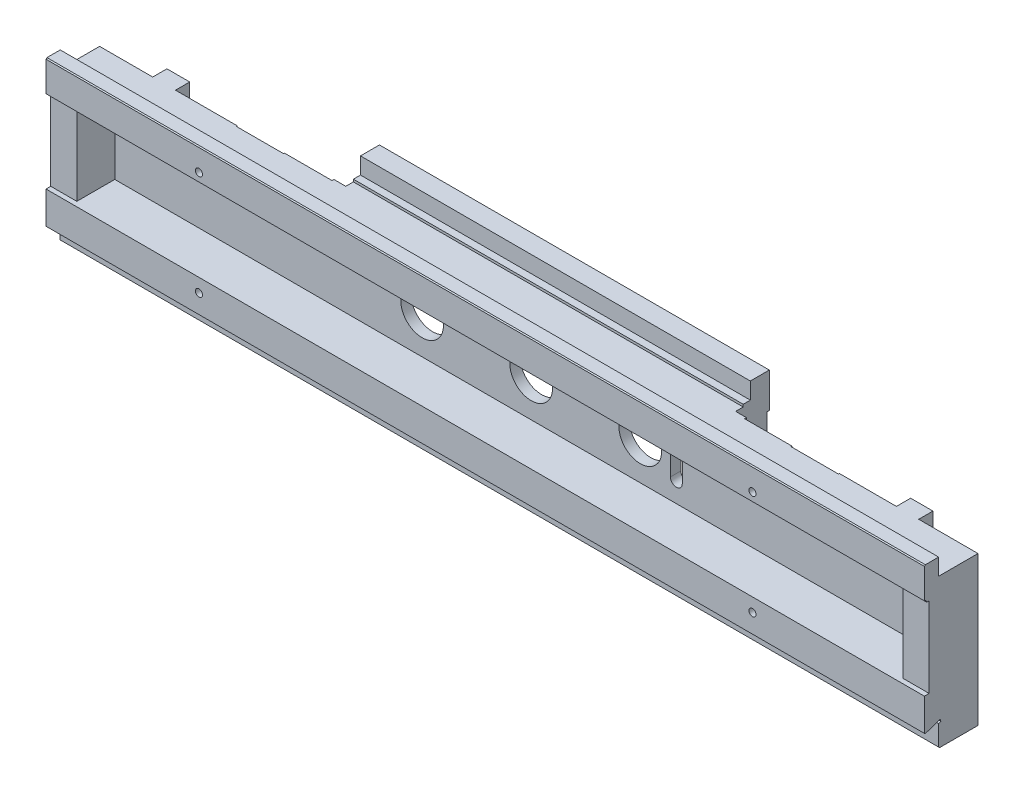
SolidWorks part; units mm, degrees
ref_plane "前视基准面" through (0, 0, 0) normal (0, 0, 1) x (1, 0, 0)
ref_plane "上视基准面" through (0, 0, 0) normal (0, 1, 0) x (1, 0, 0)
ref_plane "右视基准面" through (0, 0, 0) normal (1, 0, 0) x (0, 0, -1)
sketch "草图2" plane through (0, 0, 0) normal (1, 0, 0) x (0, 0, -1)
  line L0 (-76.2602, 62.6385) -> (-46.2602, 62.6385)
  line L1 (-46.2602, 62.6385) -> (-46.2602, 27.6385)
  line L2 (-46.2602, 27.6385) -> (36.7398, 27.6385)
  line L3 (36.7398, 27.6385) -> (36.7398, -286.3615)
  line L4 (36.7398, -286.3615) -> (-46.2602, -286.3615)
  line L5 (-46.2602, -286.3615) -> (-46.2602, -241.3615)
  line L6 (-76.2602, 62.6385) -> (-76.2602, -2.3615)
  line L9 (-66.2602, -176.3615) -> (-76.2602, -176.3615)
  line L10 (-46.2602, -241.3615) -> (-41.5305, -239.7399)
  line L11 (-41.5305, -239.7399) -> (-43.1521, -235.0102)
  line L12 (-43.1521, -235.0102) -> (-76.2602, -246.3615)
  line L13 (-76.2602, -246.3615) -> (-76.2602, -176.3615)
  line L14 (-76.2602, -2.3615) -> (-71.2602, -2.3615)
  line L15 (-71.2602, -2.3615) -> (-71.2602, -7.3574)
  line L17 (-71.2602, -7.3574) -> (-66.2602, -7.3574)
  line L18 (-66.2602, -7.3574) -> (-66.2602, -176.3615)
  dimension "D1" = 30
  dimension "D2" = 35
  dimension "D3" = 83
  dimension "D4" = 314
  dimension "D5" = 83
  dimension "D6" = 45
  dimension "D7" = 70
  dimension "D8" = 10
  dimension "D9" = 65
  dimension "D10" = 5
  dimension "D11" = 5
  dimension "D12" = 35
  dimension "D13" = 5
  dimension "D14" = 5
  dimension "D15" = 4.9959
extrude "凸台-拉伸1" add sketch "草图2" along normal blind 1852
fillet "圆角1" radius 5 1 edges at (926, -2.3615, 71.2602)
chamfer "倒角1" distance 2 angle 45 3 edges at (926, -286.3615, 46.2602) (926, -246.3615, 76.2602) (926, 62.6385, 76.2602) first distance on face at (926, -263.8615, 46.2602) first distance on face at (926, -211.3615, 76.2602) first distance on face at (926, 62.6385, 61.2602)
ref_plane "基准面1" through (1337, 0, 0) normal (1, 0, 0) x (0, 0, -1)
sketch "草图4" plane through (1337, 0, 0) normal (1, 0, 0) x (0, 0, -1)
  line L0 (36.7398, 27.6385) -> (56.7398, 27.6385)
  line L1 (56.7398, 27.6385) -> (56.7398, 32.6385)
  line L2 (56.7398, 32.6385) -> (71.7398, 32.6385)
  line L3 (71.7398, 32.6385) -> (71.7398, 67.6385)
  line L4 (71.7398, 67.6385) -> (111.7398, 67.6385)
  line L5 (111.7398, 67.6385) -> (111.7398, -326.3615)
  line L6 (111.7398, -326.3615) -> (71.7398, -326.3615)
  line L7 (71.7398, -326.3615) -> (71.7398, -291.3615)
  line L8 (71.7398, -291.3615) -> (56.7398, -291.3615)
  line L9 (56.7398, -291.3615) -> (56.7398, -286.3615)
  line L10 (56.7398, -286.3615) -> (36.7398, -286.3615)
  line L11 (36.7398, -286.3615) -> (36.7398, 27.6385)
  dimension "D1" = 20
  dimension "D2" = 5
  dimension "D3" = 15
  dimension "D4" = 35
  dimension "D5" = 40
  dimension "D6" = 20
  dimension "D7" = 5
  dimension "D8" = 15
  dimension "D9" = 35
extrude "凸台-拉伸2" add sketch "草图4" against normal blind 822
sketch "草图5" plane through (0, 0, -36.7398) normal (0, 0, -1) x (-1, 0, 0)
  line L0 (-1852, 27.6385) -> (-1337, 27.6385) construction
  line L1 (-1727, 27.6385) -> (-1680, 27.6385)
  line L2 (-1727, 27.6385) -> (-1727, -286.3615)
  line L3 (-1727, -286.3615) -> (-1680, -286.3615)
  line L4 (-1680, 27.6385) -> (-1680, -286.3615)
  line L5 (-1852, -286.3615) -> (-1337, -286.3615) construction
  line L6 (-1852, -286.3615) -> (-1852, 27.6385) construction
  dimension "D1" = 47
  dimension "D2" = 125
extrude "凸台-拉伸3" add sketch "草图5" along normal blind 30
sketch "草图7" plane through (0, 0, -36.7398) normal (0, 0, -1) x (-1, 0, 0)
  line L0 (-1680, 27.6385) -> (-1337, 27.6385) construction
  line L1 (-1560, 27.6385) -> (-1460, 27.6385)
  line L2 (-1560, 27.6385) -> (-1560, -286.3615)
  line L3 (-1560, -286.3615) -> (-1460, -286.3615)
  line L4 (-1460, 27.6385) -> (-1460, -286.3615)
  line L5 (-1680, -286.3615) -> (-1337, -286.3615) construction
  line L6 (-1680, -286.3615) -> (-1680, 27.6385) construction
  dimension "D1" = 100
  dimension "D2" = 120
extrude "切除-拉伸1" cut sketch "草图7" against normal blind 2
sketch "草图8" plane through (0, 0, -36.7398) normal (0, 0, -1) x (-1, 0, 0)
  line L0 (-1852, 27.6385) -> (0, 27.6385) construction
  line L1 (-1360, 27.6385) -> (-1337, 27.6385)
  line L2 (-1360, 27.6385) -> (-1360, -286.3615)
  line L3 (-1360, -286.3615) -> (-1337, -286.3615)
  line L4 (-1337, 27.6385) -> (-1337, -286.3615)
  line L5 (-1337, 62.15) -> (-1337, -62.15) construction
  line L6 (-1460, -286.3615) -> (-1337, -286.3615) construction
  dimension "D1" = 23
extrude "凸台-拉伸4" add sketch "草图8" along normal blind 4
sketch "草图9" plane through (0, 0, -36.7398) normal (0, 0, -1) x (-1, 0, 0)
  line L0 (-515, 27.6385) -> (0, 27.6385) construction
  line L1 (-160, 27.6385) -> (-112, 27.6385)
  line L2 (-160, 27.6385) -> (-160, -286.3615)
  line L3 (-160, -286.3615) -> (-112, -286.3615)
  line L4 (-112, 27.6385) -> (-112, -286.3615)
  line L5 (-515, -286.3615) -> (0, -286.3615) construction
  line L6 (0, -286.3615) -> (0, 27.6385) construction
  dimension "D1" = 48
  dimension "D2" = 112
extrude "凸台-拉伸5" add sketch "草图9" along normal blind 30
sketch "草图10" plane through (0, 0, -36.7398) normal (0, 0, -1) x (-1, 0, 0)
  line L0 (-515, 27.6385) -> (-160, 27.6385) construction
  line L1 (-390, 27.6385) -> (-290, 27.6385)
  line L2 (-390, 27.6385) -> (-390, -286.3615)
  line L3 (-390, -286.3615) -> (-290, -286.3615)
  line L4 (-290, 27.6385) -> (-290, -286.3615)
  line L5 (-515, -286.3615) -> (-160, -286.3615) construction
  line L6 (-160, 27.6385) -> (-160, -286.3615) construction
  dimension "D1" = 130
  dimension "D2" = 100
extrude "切除-拉伸2" cut sketch "草图10" against normal blind 2
sketch "草图11" plane through (0, 0, -36.7398) normal (0, 0, -1) x (-1, 0, 0)
  line L0 (-515, -286.3615) -> (-390, -286.3615) construction
  line L1 (-515, 27.6385) -> (-490, 27.6385)
  line L2 (-515, 27.6385) -> (-515, -286.3615)
  line L3 (-515, -286.3615) -> (-490, -286.3615)
  line L4 (-490, 27.6385) -> (-490, -286.3615)
  dimension "D1" = 25
extrude "凸台-拉伸6" add sketch "草图11" along normal blind 4
sketch "草图12" plane through (0, 0, 66.2602) normal (0, 0, 1) x (1, 0, 0)
  line L0 (1852, -7.3574) -> (0, -7.3574) construction
  line L1 (55, -7.3574) -> (1797, -7.3574)
  line L2 (55, -7.3574) -> (55, -176.3615)
  line L3 (55, -176.3615) -> (1797, -176.3615)
  line L4 (1797, -7.3574) -> (1797, -176.3615)
  line L5 (1852, -176.3615) -> (0, -176.3615) construction
  line L6 (0, -7.3574) -> (0, -176.3615) construction
  line L7 (1852, -7.3574) -> (1852, -176.3615) construction
  dimension "D1" = 55
  dimension "D2" = 55
extrude "切除-拉伸3" cut sketch "草图12" against normal blind 80
sketch "草图13" plane through (0, 0, -111.7398) normal (0, 0, -1) x (-1, 0, 0)
  line L0 (-1337, 62.15) -> (-1337, -62.15) construction
  line L1 (-1337, -6.3615) -> (-515, -6.3615)
  line L2 (-1337, -6.3615) -> (-1337, -245.3615)
  line L3 (-1337, -245.3615) -> (-515, -245.3615)
  line L4 (-515, -6.3615) -> (-515, -245.3615)
  line L5 (-515, -326.3615) -> (-515, 67.6385) construction
  line L6 (-515, 67.6385) -> (-1337, 67.6385) construction
  line L7 (-515, -326.3615) -> (-1337, -326.3615) construction
  dimension "D1" = 74
  dimension "D2" = 81
extrude "切除-拉伸4" cut sketch "草图13" against normal blind 5
sketch "草图14" plane through (0, 0, -106.7398) normal (0, 0, -1) x (-1, 0, 0)
  line L0 (-515, -6.3615) -> (-1337, -6.3615) construction
  line L1 (-1294, -16.3615) -> (-558, -16.3615)
  line L2 (-1294, -16.3615) -> (-1294, -235.3615)
  line L3 (-1294, -235.3615) -> (-558, -235.3615)
  line L4 (-558, -16.3615) -> (-558, -235.3615)
  line L5 (-1337, -245.3615) -> (-515, -245.3615) construction
  line L6 (-515, -245.3615) -> (-515, -6.3615) construction
  line L7 (-1337, 62.15) -> (-1337, -62.15) construction
  dimension "D1" = 10
  dimension "D2" = 10
  dimension "D3" = 43
  dimension "D4" = 43
extrude "切除-拉伸5" cut sketch "草图14" against normal blind 71
sketch "草图15" plane through (0, 0, -35.7398) normal (0, 0, -1) x (-1, 0, 0)
  line L0 (-1294, -16.3615) -> (-1294, -235.3615) construction
  line L6 (-558, -16.3615) -> (-1294, -16.3615) construction
  line L8 (-558, -16.3615) -> (-1294, -16.3615) construction
  line L9 (-558, -235.3615) -> (-558, -16.3615) construction
  line L11 (-1226.5, -48.8615) -> (-1226.5, -133.8615)
  line L12 (-1251.5, -48.8615) -> (-1251.5, -133.8615)
  circle A3 centre (-1163, -96.3615) radius 45
  circle A4 centre (-933, -96.3615) radius 45
  circle A5 centre (-703, -96.3615) radius 45
  arc A6 (-1226.5, -48.8615) -> (-1251.5, -48.8615) centre (-1239, -48.8615) ccw
  arc A7 (-1251.5, -133.8615) -> (-1226.5, -133.8615) centre (-1239, -133.8615) ccw
  dimension "D1" = 80
  dimension "D2" = 90
  dimension "D3" = 80
  dimension "D4" = 80
  dimension "D5" = 230
  dimension "D7" = 145
  dimension "D8" = 25
  dimension "D9" = 32.5
  dimension "D10" = 55
  dimension "D6" = 230
  dimension "D11" = 85
extrude "切除-拉伸6" cut sketch "草图15" against normal through all
sketch "草图16" plane through (0, -235.3615, 0) normal (0, 1, 0) x (1, 0, 0)
  line L0 (558, 35.7398) -> (558, 106.7398) construction
  line L1 (1294, 35.7398) -> (558, 35.7398)
  line L2 (1294, 35.7398) -> (1294, 76.7398)
  line L3 (1294, 76.7398) -> (558, 76.7398)
  line L4 (558, 35.7398) -> (558, 76.7398)
  line L5 (1337, 106.7398) -> (515, 106.7398) construction
  dimension "D1" = 30
extrude "切除-拉伸7" cut sketch "草图16" against normal blind 20
sketch "草图17" plane through (0, 0, -66.7398) normal (0, 0, -1) x (-1, 0, 0)
  line L0 (-1680, 27.6385) -> (-1727, 27.6385) construction
  line L1 (-1727, 27.6385) -> (-1727, -286.3615) construction
  line L2 (-1727, 27.6385) -> (-1727, -286.3615) construction
  line L3 (-1852, 27.6385) -> (0, 27.6385) construction
  line L4 (-112, -286.3615) -> (-112, 27.6385) construction
  line L5 (-112, -286.3615) -> (-112, 27.6385) construction
  circle A0 centre (-1707, -2.3615) radius 7.5
  circle A1 centre (-1707, -132.3615) radius 7.5
  circle A2 centre (-1707, -262.3615) radius 7.5
  circle A3 centre (-132, -2.3615) radius 7.5
  circle A4 centre (-132, -132.3615) radius 7.5
  circle A5 centre (-132, -262.3615) radius 7.5
  dimension "D1" = 15
  dimension "D2" = 15
  dimension "D3" = 15
  dimension "D10" = 15
  dimension "D11" = 15
  dimension "D12" = 15
  dimension "D13" = 30
  dimension "D4" = 30
  dimension "D5" = 20
  dimension "D6" = 20
  dimension "D7" = 130
  dimension "D8" = 20
  dimension "D9" = 130
  dimension "D14" = 20
  dimension "D15" = 20
  dimension "D16" = 20
  dimension "D17" = 130
  dimension "D18" = 130
extrude "切除-拉伸8" cut sketch "草图17" against normal up to surface (30 mm away) up to face at (1789.5, -129.3615, -36.7398)
sketch "草图18" plane through (0, 0, -36.7398) normal (0, 0, -1) x (-1, 0, 0)
  line L0 (-1489.5, -414.1296) -> (-1489.5, 345.3287) construction
  line L1 (-1460, 27.6385) -> (-1560, 27.6385) construction
  circle A0 centre (-1489.5, 15.1385) radius 7.5
  point P0 (-1489.5, 15.1385)
  point P4 (-1489.5, -34.4005)
  dimension "D2" = 15
  dimension "D1" = 12.5
extrude "切除-拉伸9" cut sketch "草图18" against normal up to surface (113 mm away) up to face at (926, 29.1385, 76.2602)
sketch "草图20" plane through (0, 0, -34.7398) normal (0, 0, -1) x (-1, 0, 0)
  line L0 (-909.5, 526.5261) -> (-909.5, -393.8437) construction
  line L1 (-909.5, 924.9493) -> (-909.5, 1662.9462) construction
sketch "草图21" plane through (0, 0, -34.7398) normal (0, 0, -1) x (-1, 0, 0)
  line L0 (-322.5, 322.0571) -> (-322.5, -334.0052) construction
  line L2 (-290, 27.6385) -> (-390, 27.6385) construction
  circle A1 centre (-322.5, 15.1385) radius 7.5
  dimension "D1" = 12.5
  dimension "D2" = 15
extrude "切除-拉伸11" cut sketch "草图21" against normal up to surface (111 mm away) up to face at (1489.5, 22.6385, 76.2602)
sketch "草图23" plane through (0, 0, -34.7398) normal (0, 0, -1) x (-1, 0, 0)
  circle A0 centre (-1489.5, -204.8615) radius 7.5
  circle A1 centre (-322.5, -204.8615) radius 7.5
extrude "切除-拉伸12" cut sketch "草图23" against normal up to surface (111 mm away) up to face at (926, -210.3615, 76.2602)
